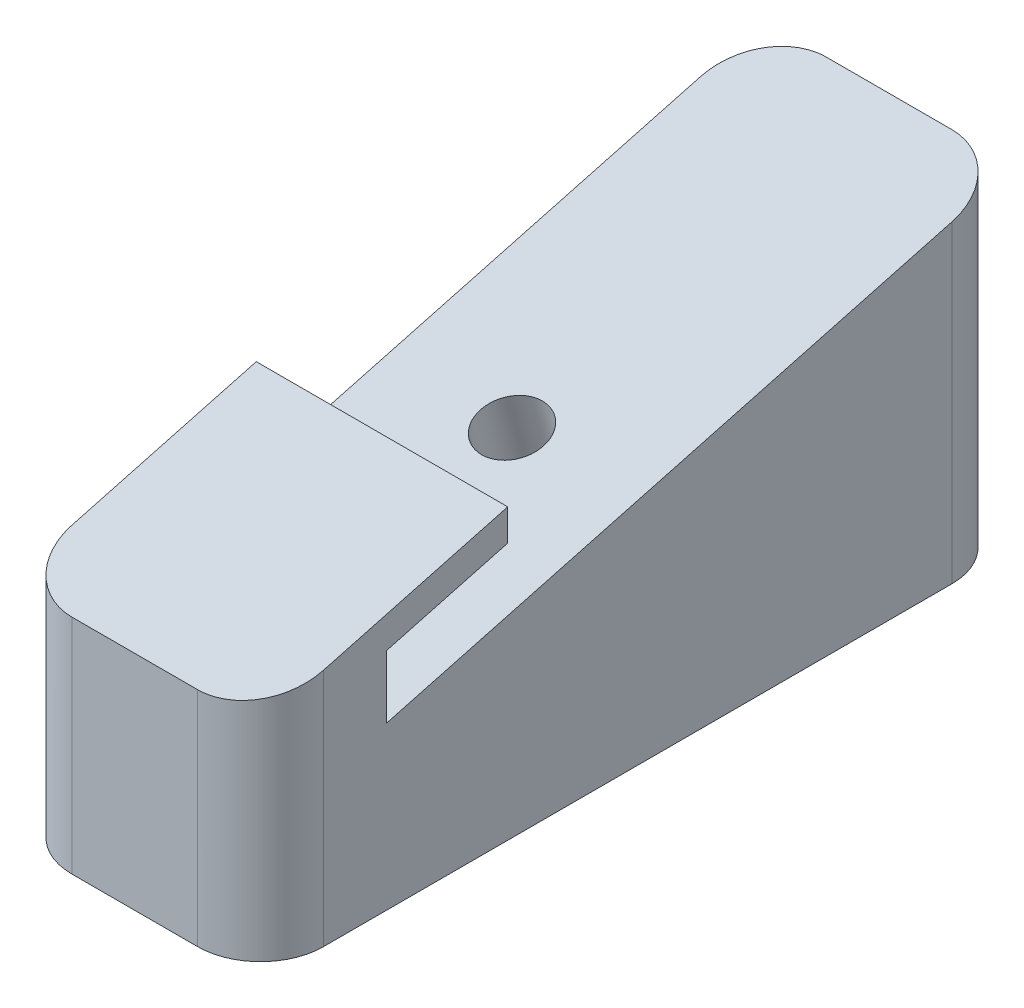
SolidWorks part; units mm, degrees
material "ABS"
ref_plane "Front Plane" through (0, 0, 0) normal (0, 0, 1) x (1, 0, 0)
ref_plane "Top Plane" through (0, 0, 0) normal (0, 1, 0) x (1, 0, 0)
ref_plane "Right Plane" through (0, 0, 0) normal (1, 0, 0) x (0, 0, -1)
sketch "Sketch1" plane through (0, 0, 0) normal (0, 1, 0) x (1, 0, 0)
  line L0 (-12.7, -25.4) -> (12.7, -25.4)
  line L1 (-12.7, -38.1) -> (12.7, -38.1)
  line L2 (-12.7, -38.1) -> (-12.7, 38.1)
  line L3 (-12.7, 38.1) -> (12.7, 38.1)
  line L4 (12.7, -38.1) -> (12.7, 38.1)
  line L5 (-12.7, -38.1) -> (12.7, 38.1) construction
  line L6 (-12.7, 38.1) -> (12.7, -38.1) construction
  point P0 (0, 0)
  dimension "D3" = 12.7
  dimension "D1" = 25.4
  dimension "D2" = 76.2
extrude "Boss-Extrude1" add sketch "Sketch1" along normal blind 33.3756 contours L1 L4 L0 L2 | L0 L4 L3 L2 region at (0, 0, -6.35) region at (0, 0, 31.75)
sketch "Sketch4" plane through (12.7, 0, 0) normal (1, 0, 0) x (0, 0, -1)
  line L0 (38.1, 33.3756) -> (-38.1, 33.3756)
  line L1 (-38.1, 33.3756) -> (-38.1, 12.9579)
  line L3 (-38.1, 12.9579) -> (38.1, 33.3756)
  line L4 (-38.1, 12.9579) -> (38.0791, 12.9579) construction
  line L6 (-38.1, 33.3756) -> (-38.1, 0) construction
  point P4 (0, 0)
  point P6 (-38.1, 33.3756)
  point P7 (38.1, 33.3756)
  point P9 (-38.1, 12.9635)
  point P14 (-38.1, 33.3756)
  point P16 (38.0791, 33.3756)
  point P17 (38.1, 33.3756)
  dimension "D1" = 15
extrude "Cut-Extrude2" cut sketch "Sketch4" against normal through all both and the other way through all
sketch "Sketch5" plane through (0, 21.6149, 5.7917) normal (0, 0.9659, 0.2588) x (1, 0, 0)
  line L0 (0, 45.44) -> (0, -33.448) construction
  line L1 (12.7, 45.44) -> (-12.7, 45.44) construction
  line L2 (-12.7, -33.448) -> (12.7, -33.448) construction
  line L3 (-12.7, 5.996) -> (12.7, 5.996) construction
  line L4 (-12.7, -33.448) -> (-12.7, 45.44) construction
  line L5 (12.7, 45.44) -> (12.7, -33.448) construction
  circle A0 centre (0, 5.996) radius 3.175
  dimension "D1" = 6.35
extrude "Cut-Extrude3" cut sketch "Sketch5" against normal blind 6.35
ref_point "Point1"
extrude "Boss-Extrude2" add sketch "Sketch1<5>" along normal blind 9.525 from surface contours L1 L4 L0 L2 region at (0, 0, 31.75) starting at face at (0, 22.345, 3.0668)
sketch "Sketch1<5>" plane through (0, 0, 0) normal (0, 1, 0) x (1, 0, 0) same geometry as "Sketch1"
sketch "Sketch7" plane through (0, 0, 25.4) normal (0, 0, -1) x (-1, 0, 0)
  line L1 (-12.7, 25.8858) -> (12.7, 25.8858)
  line L2 (-12.7, 25.8858) -> (-12.7, 22.7108)
  line L3 (-12.7, 22.7108) -> (12.7, 22.7108)
  line L4 (12.7, 25.8858) -> (12.7, 22.7108)
  line L5 (12.7, 25.8858) -> (12.7, 16.3608) construction
  point P5 (12.7, 22.4731)
  point P7 (12.7, 21.1233)
  dimension "D1" = 3.175
extrude "Boss-Extrude3" add sketch "Sketch7" along direction (0, 0.2588, -0.9659) on the side of the normal blind 12.7
fillet "Fillet1" radius 6.35 4 edges at (-12.7, 16.6878, -38.1) (-12.7, 11.2414, 38.1) (12.7, 11.2414, 38.1)
